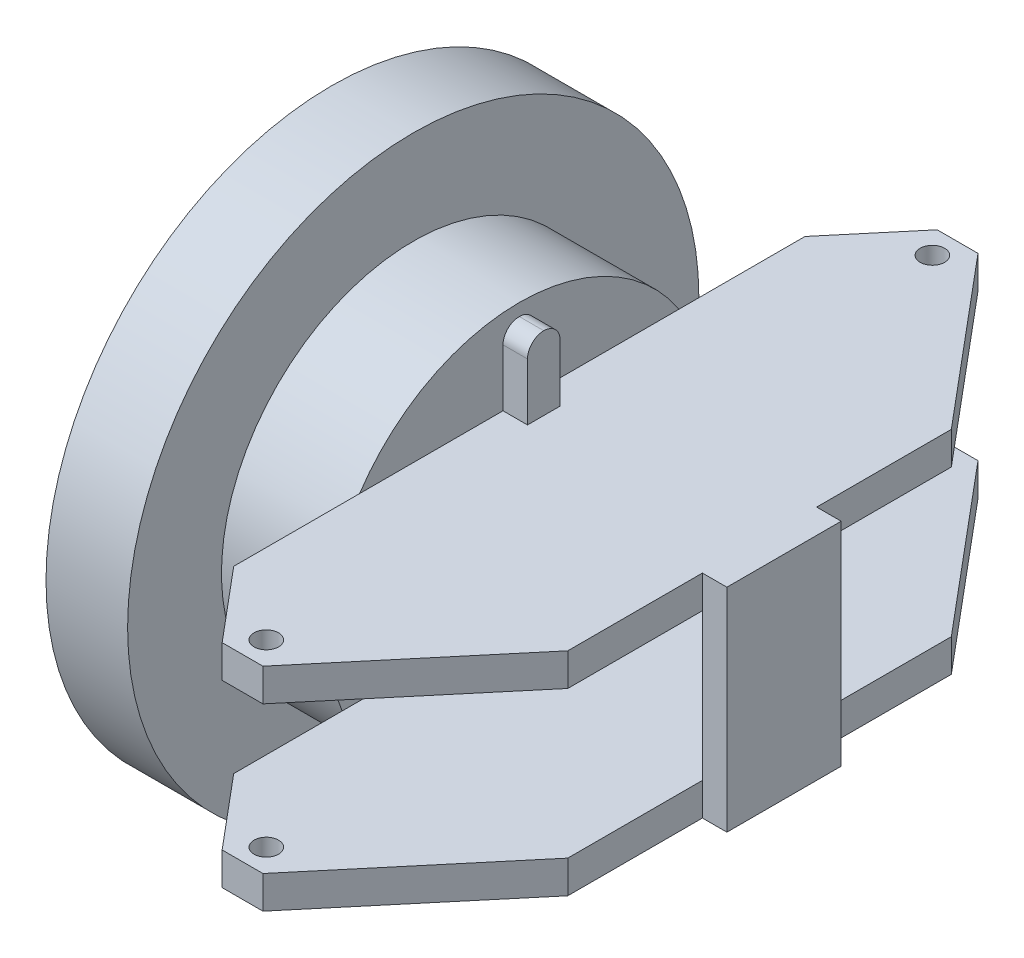
SolidWorks part; units mm, degrees
ref_plane "Front Plane" through (0, 0, 0) normal (0, 0, 1) x (1, 0, 0)
ref_plane "Top Plane" through (0, 0, 0) normal (0, 1, 0) x (1, 0, 0)
ref_plane "Right Plane" through (0, 0, 0) normal (1, 0, 0) x (0, 0, -1)
sketch "Sketch2" plane through (0, 0, 0) normal (1, 0, 0) x (0, 0, -1)
  circle A0 centre (0, 0) radius 35
  dimension "D1" = 70
extrude "Boss-Extrude1" add sketch "Sketch2" along normal blind 10
sketch "Sketch3" plane through (10, 0, 0) normal (1, 0, 0) x (0, 0, -1)
  circle A0 centre (0, 0) radius 23.5
  dimension "D1" = 47
extrude "Boss-Extrude2" add sketch "Sketch3" along normal blind 13
ref_plane "Plane1" through (0, 13, 0) normal (0, 1, 0) x (1, 0, 0)
sketch "Sketch6" plane through (0, 13, 0) normal (0, 1, 0) x (1, 0, 0)
  line L0 (23, 35) -> (23, -35)
  line L1 (23, -23.5) -> (23, 23.5) construction
  line L2 (23, -35) -> (30.3921, -43.8095)
  line L3 (30.3921, -43.8095) -> (35.3921, -43.8095)
  line L4 (35.3921, -43.8095) -> (52.4338, -23.5)
  line L5 (52.4338, -23.5) -> (52.4338, 23.5)
  line L6 (15.9541, 0) -> (60.8042, 0) construction
  line L7 (35.3921, 43.8095) -> (52.4338, 23.5)
  line L8 (30.3921, 43.8095) -> (35.3921, 43.8095)
  line L9 (23, 35) -> (30.3921, 43.8095)
  line L10 (21.1592, -23.5) -> (71.4148, -23.5) construction
  line L11 (10, -23.5) -> (23, -23.5) construction
  line L12 (21.1592, 23.5) -> (59.8408, 23.5) construction
  line L13 (23, 23.5) -> (10, 23.5) construction
  point P14 (52.4338, 0)
  point P16 (23, 0)
  dimension "D1" = 35
  dimension "D2" = 11.5
  dimension "D3" = 5
  dimension "D6" = 40
  dimension "D7" = 40
extrude "Boss-Extrude3" add sketch "Sketch6" against normal blind 4
sketch "Sketch7" plane through (0, 13, 0) normal (0, 1, 0) x (1, 0, 0)
  line L0 (30.3921, -43.8095) -> (35.3921, -43.8095) construction
  circle A0 centre (32.803, -40.8095) radius 1.5
  dimension "D1" = 3
  dimension "D2" = 3
extrude "Cut-Extrude1" cut sketch "Sketch7" against normal blind 4
mirror "Mirror1" about plane through (0, 0, 0) normal (0, 0, 1) of "Cut-Extrude1"
mirror "Mirror4" about plane through (0, 0, 0) normal (0, 1, 0) of "Mirror1", "Cut-Extrude1", "Boss-Extrude3"
sketch "Sketch8" plane through (23, 0, 0) normal (1, 0, 0) x (0, 0, -1)
  line L0 (0, 13) -> (0, 27.9059) construction
  line L1 (28.8386, 13) -> (-28.8386, 13) construction
  line L2 (-2, 13) -> (-2, 22)
  line L3 (-2, 22) -> (2, 22)
  line L4 (2, 22) -> (2, 13)
  line L5 (2, 13) -> (-2, 13)
  dimension "D1" = 9
  dimension "D2" = 2
  dimension "D3" = 2
extrude "Boss-Extrude4" add sketch "Sketch8" along normal blind 3
fillet "Fillet1" radius 2 2 edges at (24.5, 22, -2) (24.5, 22, 2)
mirror "Mirror5" about plane through (0, 0, 0) normal (0, 1, 0) of "Fillet1", "Boss-Extrude4"
sketch "Sketch9" plane through (52.4338, 0, 0) normal (1, 0, 0) x (0, 0, -1)
  line L1 (-7, 13) -> (7, 13)
  line L2 (-7, 13) -> (-7, -13)
  line L3 (-7, -13) -> (7, -13)
  line L4 (7, 13) -> (7, -13)
  line L5 (-7, 13) -> (7, -13) construction
  line L6 (-7, -13) -> (7, 13) construction
  point P0 (0, 0)
  dimension "D1" = 26
  dimension "D2" = 14
extrude "Boss-Extrude5" add sketch "Sketch9" along normal blind 3
sketch "Sketch10" plane through (0, 0, 0) normal (-1, 0, 0) x (0, 0, 1)
  circle A0 centre (0, 0) radius 10
  dimension "D1" = 20
extrude "Cut-Extrude2" cut sketch "Sketch10" against normal blind 10
ref_point "Point1"
